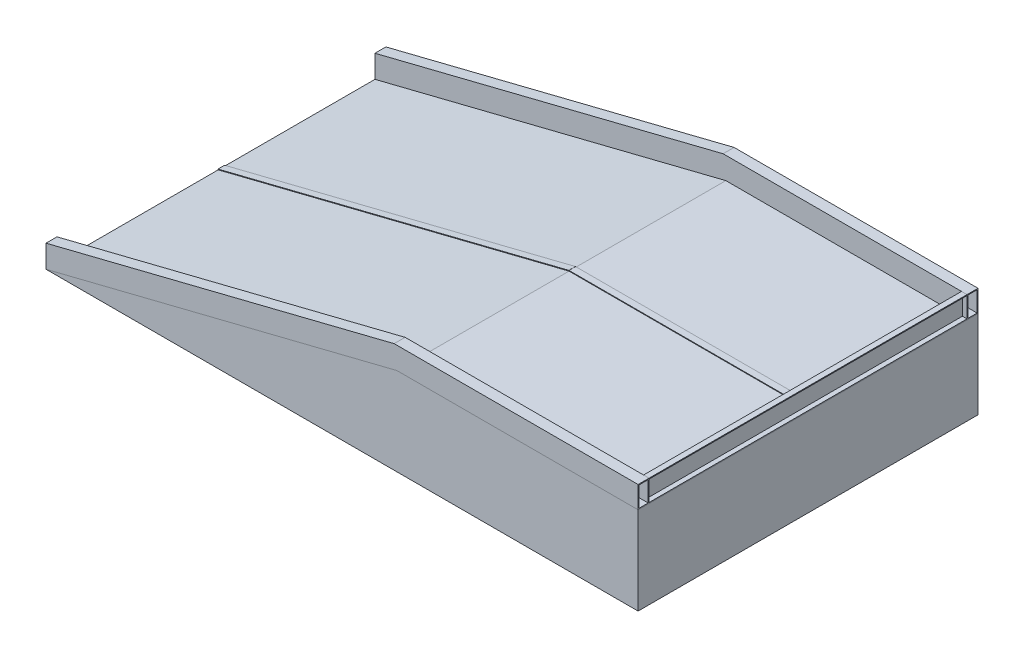
SolidWorks part; units mm, degrees
ref_plane "Front Plane" through (0, 0, 0) normal (0, 0, 1) x (1, 0, 0)
ref_plane "Top Plane" through (0, 0, 0) normal (0, 1, 0) x (1, 0, 0)
ref_plane "Right Plane" through (0, 0, 0) normal (1, 0, 0) x (0, 0, -1)
sketch "Sketch1" plane through (0, 0, 0) normal (0, 0, 1) x (1, 0, 0)
  line L0 (-2700, 0) -> (0, 0)
  line L1 (-2700, 0) -> (-1100, 400)
  line L2 (-1100, 400) -> (0, 400)
  line L4 (0, 0) -> (0, 400)
  dimension "D1" = 1600
  dimension "D2" = 2700
  dimension "D3" = 400
extrude "Boss-Extrude1" add sketch "Sketch1" along normal blind 775 and the other way blind 775
sketch "Sketch3" plane through (0, 0, 775) normal (0, 0, 1) x (1, 0, 0)
  line L0 (-2700, 0) -> (-2700, 103.0776)
  line L1 (-2700, 103.0776) -> (-1112.3106, 500)
  line L3 (-1100, 400) -> (-2700, 0)
  line L4 (-1100, 400) -> (-2700, 0) construction
  line L5 (0, 0) -> (0, 400) construction
  line L6 (-1150, 500) -> (0, 500)
  line L8 (-1150, 400) -> (0, 400)
  line L9 (0, 500) -> (0, 400)
  line L10 (0, 400) -> (-1100, 400) construction
  line L11 (-1150, 500) -> (-1112.3106, 500)
  line M9 (-1100, 400) -> (-2700, 0)
  line M12 (0, 400) -> (-1100, 400)
  dimension "D1" = 100
  dimension "D2" = 0
  dimension "D3" = 0
  dimension "D4" = 0
  dimension "D5" = 100
  dimension "D7" = 0
  dimension "D8" = 0
extrude "Boss-Extrude2" add sketch "Sketch3" against normal blind 50 separate body contours L6 L11 L1 L0 L9 M9 M12 region at (-2672.5409, 51.5388, 775)
shell "Shell1" thickness 4 removed face at (0, 450, 750) removed face at (-2700, 51.5388, 750)
sketch "Sketch4" plane through (0, 0, -775) normal (0, 0, -1) x (-1, 0, 0)
  line L0 (1100, 400) -> (2700, 0) construction
  line L1 (0, 400) -> (1100, 400) construction
  line L2 (2700, 0) -> (2700, 103.0776)
  line L3 (2700, 103.0776) -> (1112.3106, 500) construction
  line L5 (0, 500) -> (0, 400) construction
  line L6 (1100, 400) -> (2700, 0)
  line L7 (0, 400) -> (1100, 400)
  line L9 (2700, 103.0776) -> (1112.3106, 500)
  line L10 (1112.3106, 500) -> (0, 500)
  line L11 (0, 500) -> (0, 400)
  point P6 (0, 0)
  point P13 (0, 0)
extrude "Boss-Extrude3" add sketch "Sketch4" against normal blind 50 separate body
shell "Shell2" thickness 4 removed face at (0, 450, -750) removed face at (-2700, 51.5388, -750)
sketch "Sketch5" plane through (0, 400, 0) normal (0, 1, 0) x (1, 0, 0)
  line L0 (0, 775) -> (0, -775) construction
  line L1 (-25, 725) -> (0, 725)
  line L2 (-25, 725) -> (-25, -725)
  line L3 (-25, -725) -> (0, -725)
  line L4 (0, 725) -> (0, -725)
  line L5 (-1112.3106, 725) -> (0, 725) construction
  line L7 (-1100, -725) -> (-2700, -725) construction
  dimension "D1" = 25
  dimension "D2" = 0
  dimension "D3" = 0
extrude "Boss-Extrude4" add sketch "Sketch5" along normal blind 100 separate body
shell "Shell3" thickness 4 removed face at (-12.5, 450, -725) removed face at (0, 450, 0) removed face at (-12.5, 450, 725)
sketch "Sketch7" plane through (0, 400, 0) normal (0, 1, 0) x (1, 0, 0)
  line L0 (-25, 725) -> (-25, -725) construction
  line L1 (-1100, 40) -> (-25, 40)
  line L2 (-1100, 40) -> (-1100, 10)
  line L3 (-1100, 10) -> (-25, 10)
  line L4 (-25, 40) -> (-25, 10)
  line L5 (-1100, 775) -> (-1100, -775) construction
  line L7 (0, -725) -> (-1100, -725) construction
  dimension "D1" = 30
  dimension "D2" = 0
  dimension "D3" = 0
  dimension "D4" = 735
extrude "Boss-Extrude5" add sketch "Sketch7" along normal blind 3 separate body
sketch "Sketch8" plane through (-158.8235, 635.2941, 0) normal (-0.2425, 0.9701, 0) x (0.9701, 0.2425, 0)
  line L0 (73.4883, 40) -> (-969.4149, 40) construction
  line L1 (-2619.3848, 40) -> (-970.1425, 40)
  line L2 (-2619.3848, 40) -> (-2619.3848, 10)
  line L3 (-2619.3848, 10) -> (-970.1425, 10)
  line L4 (-970.1425, 40) -> (-970.1425, 10)
  line L5 (-970.1425, 775) -> (-970.1425, -775) construction
  line L6 (-2619.3848, 775) -> (-2619.3848, -775) construction
  point P8 (-2619.3848, 25)
  dimension "D1" = 30
  dimension "D2" = 0
  dimension "D3" = 0
  dimension "D4" = 0
extrude "Boss-Extrude6" add sketch "Sketch8" along normal blind 3 separate body
